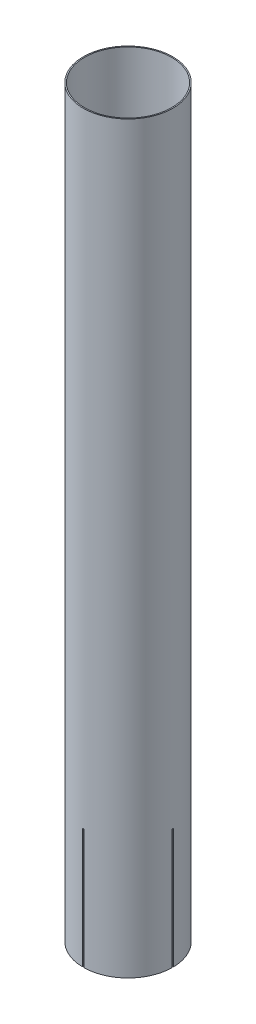
SolidWorks part; units mm, degrees
ref_plane "Front Plane" through (0, 0, 0) normal (0, 0, 1) x (1, 0, 0)
ref_plane "Top Plane" through (0, 0, 0) normal (0, 1, 0) x (1, 0, 0)
ref_plane "Right Plane" through (0, 0, 0) normal (1, 0, 0) x (0, 0, -1)
sketch "Sketch1" plane through (0, 0, 0) normal (0, 0, 1) x (1, 0, 0)
  line L0 (78.2, 0) -> (78.2, 1300)
  line L1 (0, 0) -> (0, 2000) construction
  line L9 (76.2, 0) -> (76.2, 1300)
  line L10 (78.2, 0) -> (76.2, 0)
  line L11 (78.2, 1300) -> (76.2, 1300)
  point P7 (65, 1600)
  point P8 (-1029.1667, 1600)
  point P9 (-9.3208, 1996.3774)
  dimension "D1" = 1300
  dimension "D2" = 76.2
  dimension "D3" = 2000
  dimension "D4" = 2
revolve "Revolve1" add sketch "Sketch1" angle 360 about L1
sketch "Sketch2" plane through (0, 0, 0) normal (0, 0, 1) x (1, 0, 0)
  line L0 (-185.2, 150) -> (-185.2, 0)
  line L1 (-185.2, 0) -> (-78.2, 0)
  line L2 (-78.2, 0) -> (-78.2, 210) construction
  line L3 (-78.2, 210) -> (-185.2, 150)
  line L4 (-78.2, 0) -> (0, 0)
  line L5 (-78.2, 210) -> (0, 210)
  line L6 (0, 0) -> (0, 210)
  dimension "D1" = 210
  dimension "D2" = 150
  dimension "D3" = 107
extrude "Cut-Extrude1" cut sketch "Sketch2" against normal blind 1.5 and the other way blind 1.5
pattern_circular "CirPattern1" count 4 over 360 about axis through (0, 0, 0) along (0, -1, 0) of "Cut-Extrude1"
